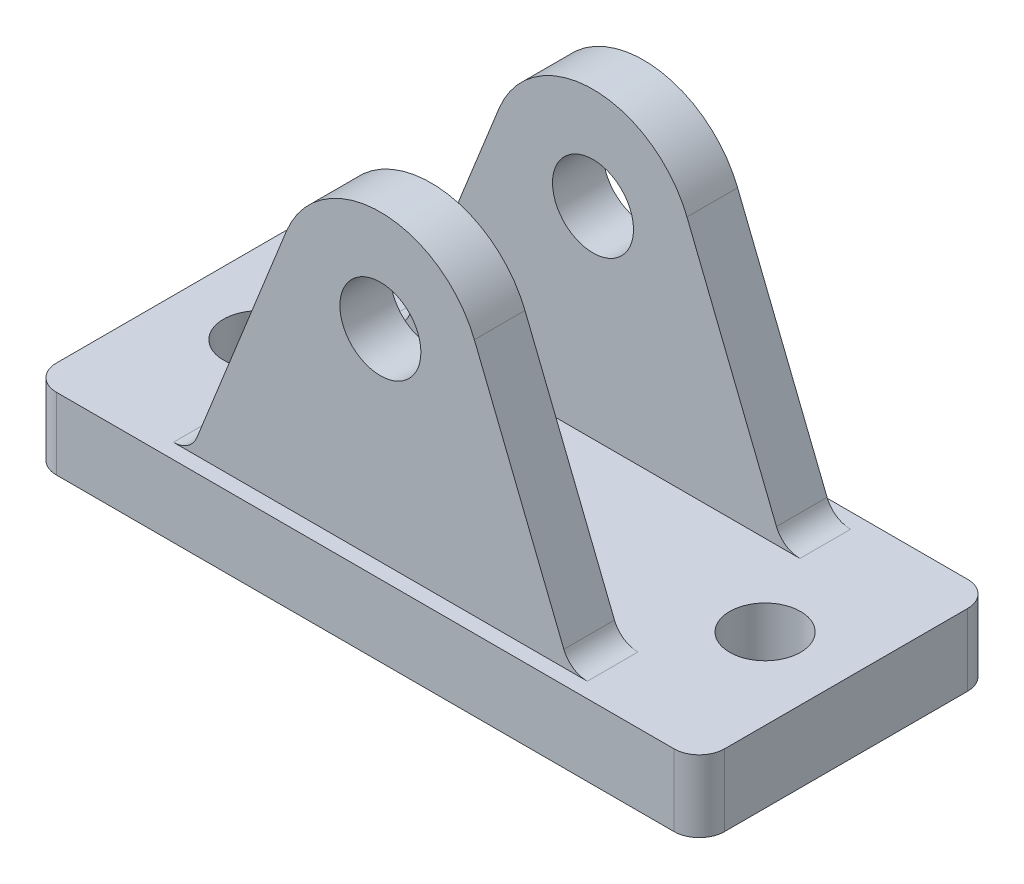
SolidWorks part; units mm, degrees
material "AISI 1020"
ref_plane "Front Plane" through (0, 0, 0) normal (0, 0, 1) x (1, 0, 0)
ref_plane "Top Plane" through (0, 0, 0) normal (0, 1, 0) x (1, 0, 0)
ref_plane "Right Plane" through (0, 0, 0) normal (1, 0, 0) x (0, 0, -1)
sketch "Sketch1" plane through (0, 0, 0) normal (0, 1, 0) x (1, 0, 0)
  line L0 (0, 29) -> (0, 0) construction
  line L1 (-66, -29) -> (66, -29)
  line L2 (-66, -29) -> (-66, 29)
  line L3 (-66, 29) -> (66, 29)
  line L4 (66, -29) -> (66, 29)
  line L5 (-66, -29) -> (66, 29) construction
  line L6 (-66, 29) -> (66, -29) construction
  point P0 (0, 0)
  point P12 (0, 0)
  point P13 (66, -29)
  dimension "D1" = 58
  dimension "D2" = 132
extrude "Boss-Extrude1" add sketch "Sketch1" along normal blind 14.1676 contours L1 L4 L3 L2
sketch "Sketch2" plane through (0, 14.1676, 0) normal (0, 1, 0) x (1, 0, 0)
  line L0 (0, 0) -> (0, 29) construction
  line L1 (-66, 29) -> (66, 29) construction
  line L2 (-66, -29) -> (-66, 29) construction
  circle A0 centre (-50, 0) radius 7
  circle A1 centre (50, 0) radius 7
  point P11 (0, 0)
  dimension "D1" = 16
  dimension "D2" = 14
extrude "Cut-Extrude1" cut sketch "Sketch2" against normal through all
sketch "Sketch3" plane through (0, 0, 0) normal (0, 0, 1) x (1, 0, 0)
  line L0 (37.5, 14.1676) -> (-37.5, 14.1676)
  line L1 (-66, 14.1676) -> (66, 14.1676) construction
  line L2 (-37.5, 14.1676) -> (-18.566, 61.4367)
  line L3 (18.566, 61.4367) -> (37.5, 14.1676)
  arc A0 (-18.566, 61.4367) -> (18.566, 61.4367) centre (0, 54) cw
  point P7 (0, 0)
  dimension "D1" = 20
  dimension "D2" = 54
  dimension "D3" = 75
extrude "Boss-Extrude2" add sketch "Sketch3" along normal blind 10 from offset 16
sketch "Sketch4" plane through (0, 0, 26) normal (0, 0, 1) x (1, 0, 0)
  circle A0 centre (0, 54) radius 8
  arc A1 (18.566, 61.4367) -> (-18.566, 61.4367) centre (0, 54) ccw construction
  dimension "D1" = 16
extrude "Cut-Extrude2" cut sketch "Sketch4" against normal up to next
extrude "Boss-Extrude3" add sketch "Sketch3<2>" against normal blind 10 from offset 16 offset against normal yes
sketch "Sketch3<2>" plane through (0, 0, 0) normal (0, 0, 1) x (1, 0, 0) same geometry as "Sketch3"
sketch "Sketch5" plane through (0, 0, -26) normal (0, 0, -1) x (-1, 0, 0)
  circle A0 centre (0, 54) radius 8
  arc A1 (18.566, 61.4367) -> (-18.566, 61.4367) centre (0, 54) ccw construction
  dimension "D1" = 16
extrude "Cut-Extrude3" cut sketch "Sketch5" against normal up to next
fillet "Fillet1" radius 5 8 edges at (-37.5, 14.1676, -21) (37.5, 14.1676, -21) (37.5, 14.1676, 21) (-37.5, 14.1676, 21) (-66, 7.0838, -29) (66, 7.0838, -29) (-66, 7.0838, 29) (66, 7.0838, 29)
